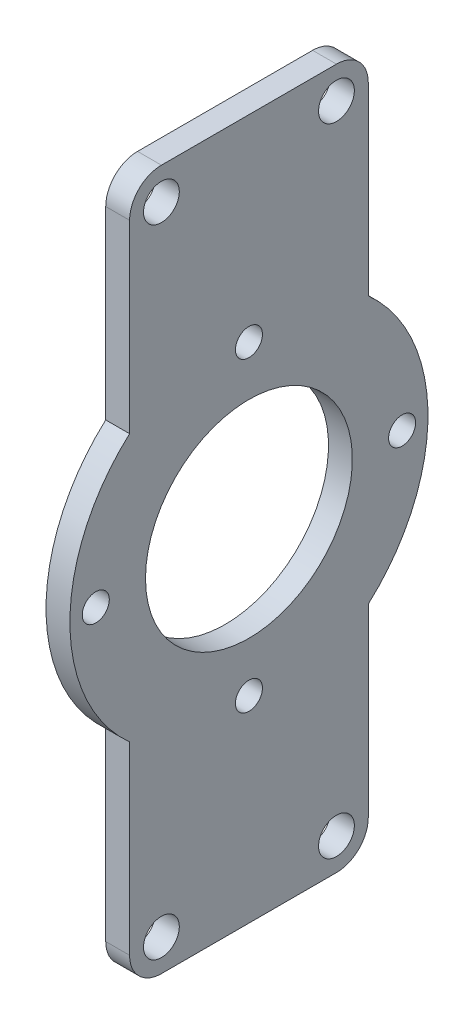
SolidWorks part; units mm, degrees
ref_plane "Спереди" through (0, 0, 0) normal (0, 0, 1) x (1, 0, 0)
ref_plane "Сверху" through (0, 0, 0) normal (0, 1, 0) x (1, 0, 0)
ref_plane "Справа" through (0, 0, 0) normal (1, 0, 0) x (0, 0, -1)
sketch "Эскиз1" plane through (0, 0, 0) normal (0, 1, 0) x (1, 0, 0)
  line L1 (0, 0) -> (3, 0)
  line L2 (0, 0) -> (0, -30)
  line L3 (0, -30) -> (3, -30)
  line L4 (3, 0) -> (3, -30)
  dimension "D1" = 3
  dimension "D2" = 30
extrude "Бобышка-Вытянуть1" add sketch "Эскиз1" along normal blind 88
sketch "Эскиз2" plane through (0, 0, 0) normal (-1, 0, 0) x (0, 0, 1)
  line L0 (30, 44) -> (0, 44) construction
  line L1 (30, 88) -> (30, 0) construction
  line L2 (0, 88) -> (0, 0) construction
  line L3 (15, 88) -> (15, 0) construction
  line L4 (0, 88) -> (30, 88) construction
  line L5 (0, 0) -> (30, 0) construction
  circle A0 centre (15, 44) radius 22.5
  dimension "D1" = 45
extrude "Бобышка-Вытянуть2" add sketch "Эскиз2" against normal up to surface (3 mm away) up to face at (3, 44, 15)
sketch "Эскиз3" plane through (0, 0, 0) normal (-1, 0, 0) x (0, 0, 1)
  circle A0 centre (15, 44) radius 13
  dimension "D1" = 26
extrude "Вырез-Вытянуть1" cut sketch "Эскиз3" against normal through all
sketch "Эскиз4" plane through (3, 0, 0) normal (-1, 0, 0) x (0, 0, 1)
  line L0 (15, 66.5) -> (15, 21.5) construction
  line L1 (15, 88) -> (15, 0) construction
  line L2 (37.5, 44) -> (-7.5, 44) construction
  circle A0 centre (15, 44) radius 19.25 construction
  circle A1 centre (15, 44) radius 22.5 construction
  dimension "D1" = 38.5
hole_wizard "Отверстие с зазором M31" positions "Эскиз6" profile "Эскиз5" hole size "M3" standard "Ansi Metric" end condition through all
sketch "Эскиз6" plane through (3, -25.0247, 7.2629) normal (-1, 0, 0) x (0, 0, 1)
  line L0 (7.7371, 91.5247) -> (7.7371, 46.5247) construction
  line L1 (30.2371, 69.0247) -> (-14.7629, 69.0247) construction
  circle A0 centre (7.7371, 69.0247) radius 19.25 construction
  point P0 (7.7371, 88.2747)
  point P6 (-11.5129, 69.0247)
  point P10 (7.7371, 49.7747)
  point P12 (26.9871, 69.0247)
sketch "Эскиз5" plane through (3, 63.25, 15) normal (0, 1, 0) x (0, 0, -1)
  line L0 (0, 0) -> (0, 3)
  line L1 (0, 3) -> (1.7, 3)
  line L2 (1.7, 3) -> (1.7, 0)
  line L5 (1.7, 0) -> (0, 0)
  line L11 (0, -6.35) -> (0, 107.95) construction
  dimension "Диаметр сквозного отверстия" = 3.4
  dimension "Глубина сквозного отверстия" = 3
sketch "Эскиз8" plane through (3, 0, 0) normal (1, 0, 0) x (0, 0, -1)
  line L0 (-15, 88) -> (-15, 0) construction
  line L1 (-30, 88) -> (0, 88) construction
  line L2 (-30, 0) -> (0, 0) construction
  line L3 (19.447, 44) -> (-49.447, 44) construction
  line L4 (0, 88) -> (0, 60.7705) construction
  line L5 (-26, 84) -> (-4, 84) construction
  line L6 (-26, 84) -> (-26, 4) construction
  line L7 (-26, 4) -> (-4, 4) construction
  line L8 (-4, 84) -> (-4, 4) construction
  line L9 (-26, 84) -> (-4, 4) construction
  line L10 (-26, 4) -> (-4, 84) construction
  line L11 (0, 0) -> (-30, 0) construction
  point P8 (-15, 44)
  point P9 (-15, 44)
  dimension "D1" = 4
  dimension "D2" = 4
  dimension "D3" = 80
  dimension "D4" = 22
hole_wizard "Отверстие с зазором M41" positions "Эскиз10" profile "Эскиз9" hole size "M4" standard "Ansi Metric" end condition through all
sketch "Эскиз10" plane through (3, 0, 0) normal (1, 0, 0) x (0, 0, -1)
  point P0 (-26, 84)
  point P3 (-4, 84)
  point P6 (-4, 4)
  point P9 (-26, 4)
sketch "Эскиз9" plane through (3, 84, 26) normal (0, 1, 0) x (0, 0, -1)
  line L0 (0, 0) -> (0, 3)
  line L1 (0, 3) -> (2.25, 3)
  line L2 (2.25, 3) -> (2.25, 0)
  line L5 (2.25, 0) -> (0, 0)
  line L11 (0, -6.35) -> (0, 107.95) construction
  dimension "Диаметр сквозного отверстия" = 4.5
  dimension "Глубина сквозного отверстия" = 3
fillet "Скругление1" radius 4 4 edges at (1.5, 0, 0) (1.5, 0, 30) (1.5, 88, 30) (1.5, 88, 0)
